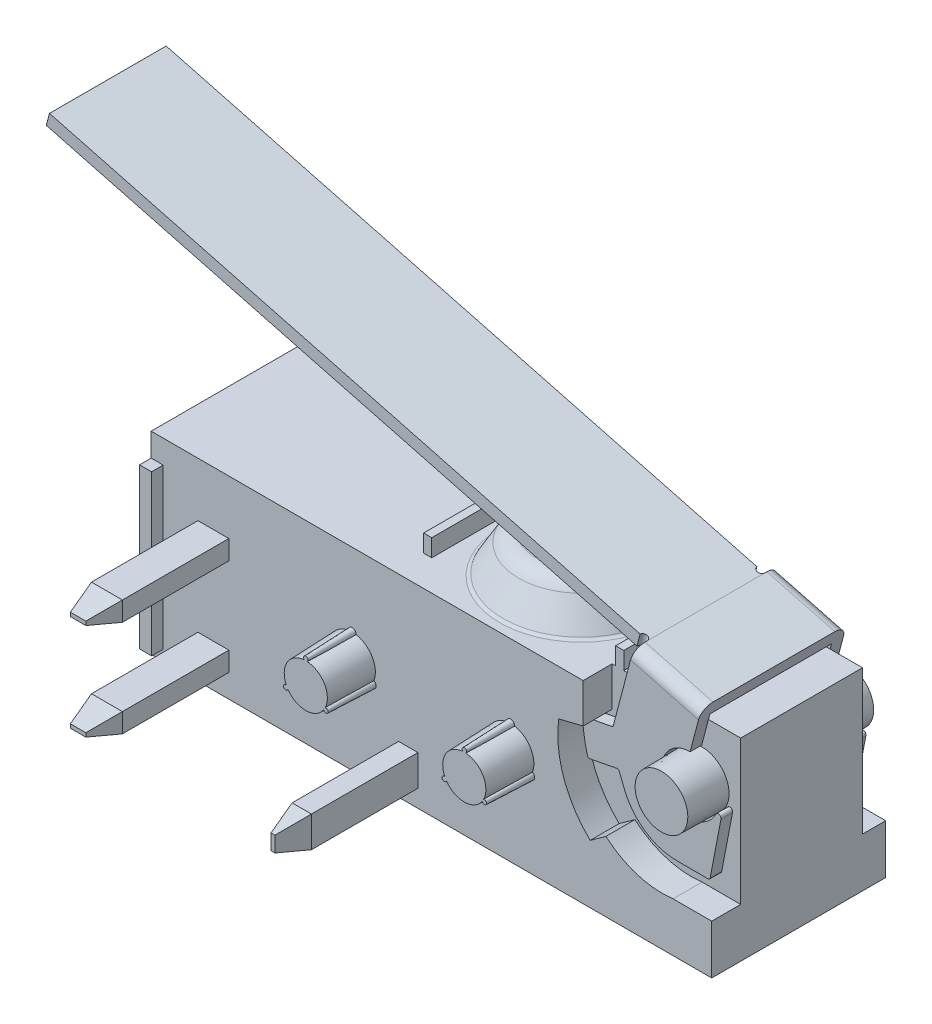
SolidWorks part; units mm, degrees
ref_plane "Front Plane" through (0, 0, 0) normal (0, 0, 1) x (1, 0, 0)
ref_plane "Top Plane" through (0, 0, 0) normal (0, 1, 0) x (1, 0, 0)
ref_plane "Right Plane" through (0, 0, 0) normal (1, 0, 0) x (0, 0, -1)
sketch "Sketch1" plane through (0, 0, 0) normal (0, 0, 1) x (1, 0, 0)
  line L0 (0, 0) -> (0, -2.5) construction
  line L1 (0, -2.5) -> (5.2, -2.5)
  line L2 (5.2, -2.5) -> (5.2, 2.5)
  line L3 (5.2, 2.5) -> (-9.3, 2.5)
  line L4 (-9.3, 2.5) -> (-9.3, -2.5)
  line L5 (0, -2.5) -> (-9.3, -2.5)
  dimension "D1" = 2.5
  dimension "D2" = 5.2
  dimension "D3" = 5
  dimension "D4" = 14.5
extrude "Boss-Extrude1" add sketch "Sketch1" against normal blind 4.5
sketch "Sketch2" plane through (0, 0, 0) normal (0, 0, 1) x (1, 0, 0)
  line L0 (0, 0) -> (0, 0.6) construction
  line L1 (0, 0) -> (0.5196, -0.3) construction
  line L2 (0, 0) -> (0, -2.5) construction
  line L3 (-9.3, -2.5) -> (5.2, -2.5) construction
  line L4 (-4.1, 0) -> (-4.1, -2.5)
  line L5 (-4.1, 0) -> (-3.5804, -0.3) construction
  line L6 (-4.1, 0) -> (-4.1, 0.6) construction
  arc A0 (-0.0997, 0.5917) -> (-0.5622, -0.2095) centre (0, 0) ccw
  arc A1 (-4.6622, -0.2095) -> (-4.5626, -0.3821) centre (-4.6196, -0.3) ccw
  arc A2 (0.0997, 0.5917) -> (-0.0997, 0.5917) centre (0, 0.6) ccw
  arc A3 (0.4626, -0.3821) -> (0.5622, -0.2095) centre (0.5196, -0.3) ccw
  arc A4 (-0.5622, -0.2095) -> (-0.4626, -0.3821) centre (-0.5196, -0.3) ccw
  arc A5 (-0.4626, -0.3821) -> (0.4626, -0.3821) centre (0, 0) ccw
  arc A6 (0.5622, -0.2095) -> (0.0997, 0.5917) centre (0, 0) ccw
  arc A7 (-3.5378, -0.2095) -> (-4.0003, 0.5917) centre (-4.1, 0) ccw
  arc A8 (-4.0003, 0.5917) -> (-4.1997, 0.5917) centre (-4.1, 0.6) ccw
  arc A9 (-4.1997, 0.5917) -> (-4.6622, -0.2095) centre (-4.1, 0) ccw
  arc A10 (-3.6374, -0.3821) -> (-3.5378, -0.2095) centre (-3.5804, -0.3) ccw
  arc A11 (-4.5626, -0.3821) -> (-3.6374, -0.3821) centre (-4.1, 0) ccw
  dimension "D1" = 3
  dimension "D2" = 120
  dimension "D3" = 0.6
  dimension "D4" = 4.1
extrude "Boss-Extrude3" add sketch "Sketch2" along normal blind 1.2 draft 2 contours A1 A11 A10 A7 A8 A9 | A3 A6 A2 A0 A4 A5 region at (0, 0, 0) region at (-4.6041, 0.291, 0)
sketch "Sketch3" plane through (0, 0, 0) normal (0, 0, 1) x (1, 0, 0)
  line L0 (0, 0) -> (0, -2.5) construction
  line L1 (-9.3, -2.5) -> (5.2, -2.5) construction
  line L3 (-9.3, -2.5) -> (5.2, -2.5)
  line L5 (-2.9, -2.05) -> (-2.9, -1.25)
  line L6 (-7.29, -1.9) -> (-7.29, -1.4)
  line L7 (-8.09, -1.9) -> (-8.09, -1.4)
  line L8 (-2.9, -1.25) -> (-2.4, -1.25)
  line L9 (-2.4, -2.05) -> (-2.4, -1.25)
  line L10 (-2.9, -2.05) -> (-2.4, -2.05)
  line L11 (-7.29, -1.4) -> (-8.09, -1.4)
  line L12 (-7.29, -1.9) -> (-8.09, -1.9)
  line L13 (-7.69, -1.9) -> (-7.69, -1.65) construction
  line L14 (-7.69, 0.6) -> (-7.69, 0.85) construction
  line L15 (-7.29, 1.1) -> (-8.09, 1.1)
  line L16 (-8.09, 0.6) -> (-8.09, 1.1)
  line L17 (-7.29, 0.6) -> (-7.29, 1.1)
  line L18 (-7.29, 0.6) -> (-8.09, 0.6)
  point P5 (-2.65, 0)
  point P6 (-2.65, -2.5)
  point P7 (-9.3, -1.65)
  point P8 (5.2, -1.65)
  point P17 (-2.9, -1.65)
  point P23 (-7.69, -1.9)
  point P29 (-7.69, 0.6)
extrude "Boss-Extrude4" add sketch "Sketch3" along normal blind 3.5 separate body contours L5 L10 L9 L8 | L12 L6 L11 L7 | L18 L17 L15 L16 region at (-2.65, -1.65, 0) region at (-7.69, -1.65, 0) region at (-7.69, 0.85, 0)
chamfer "Chamfer1" distance 0.2 angle 75 4 edges at (-2.65, -1.25, 3.5) (-2.4, -1.65, 3.5) (-2.65, -2.05, 3.5) (-2.9, -1.65, 3.5) first distance on face at (-2.65, -1.65, 3.5)
chamfer "Chamfer2" distance 0.2 angle 75 4 edges at (-7.69, 0.6, 3.5) (-7.29, 0.85, 3.5) (-7.69, 1.1, 3.5) (-8.09, 0.85, 3.5) first distance on face at (-7.69, 0.85, 3.5)
chamfer "Chamfer3" distance 0.2 angle 75 4 edges at (-7.69, -1.4, 3.5) (-7.29, -1.65, 3.5) (-7.69, -1.9, 3.5) (-8.09, -1.65, 3.5) first distance on face at (-7.69, -1.65, 3.5)
sketch "Sketch5" plane through (0, 0, 0) normal (0, 0, 1) x (1, 0, 0)
  line L0 (1.8737, 2.5) -> (5.2, 2.5)
  line L3 (5.2, -1.2263) -> (4.2, -1.2263)
  line L5 (1.8737, 1.4816) -> (1.8737, 2.5)
  line L6 (1.8737, 1.4816) -> (1.242, 1.3256)
  line L7 (5.2, 2.5) -> (5.2, -1.2263)
  line L8 (2.0554, -0.9882) -> (2.4632, -0.6956)
  arc A0 (1.242, 1.3256) -> (2.0554, -0.9882) centre (3.9209, 0.9675) ccw
  arc A1 (2.4632, -0.6956) -> (4.2, -1.2263) centre (3.9209, 0.9675) ccw
  line M9 (5.2, -2.5) -> (5.2, 2.5)
  line M10 (5.2, 2.5) -> (-9.3, 2.5)
extrude "Cut-Extrude1" cut sketch "Sketch5" against normal blind 0.75 from surface contours L8 A1 L3 L5 L6 A0 M9 M10 region at (3.4128, 0.6847, 0) starting at face at (-4.1, 0, 0)
sketch "Sketch6" plane through (0, 0, -0.75) normal (0, 0, 1) x (1, 0, 0)
  line L0 (0, 0) -> (0, 2.5) construction
  line L1 (1.8737, 2.5) -> (-9.3, 2.5) construction
  circle A0 centre (4.2, 1.1) radius 0.7
extrude "Boss-Extrude6" add sketch "Sketch6" along normal blind 1.05 draft 1
sketch "Sketch7" plane through (0, 0, -4.5) normal (0, 0, -1) x (-1, 0, 0)
  line L1 (-1.8737, 1.4816) -> (-1.8737, 2.5) construction
  line L2 (-1.8737, 2.5) -> (-5.2, 2.5) construction
  line L3 (-5.2, 2.5) -> (-5.2, -1.2263) construction
  line L4 (-5.2, -1.2263) -> (-4.2, -1.2263) construction
  line L5 (-2.0554, -0.9882) -> (-2.4632, -0.6956) construction
  line L6 (-1.8737, 1.4531) -> (-1.2749, 1.2919)
  line L7 (-1.8737, 1.4531) -> (-1.8737, 2.5)
  line L8 (-1.8737, 2.5) -> (-5.2, 2.5)
  line L9 (-5.2, 2.5) -> (-5.2, -1.2263)
  line L10 (-5.2, -1.2263) -> (-4.2, -1.2263)
  line L11 (-2.086, -0.9663) -> (-2.4632, -0.6956)
  arc A0 (-4.2, -1.2263) -> (-2.4632, -0.6956) centre (-3.9209, 0.9675) ccw construction
  arc A2 (-4.2, -1.2263) -> (-2.4632, -0.6956) centre (-3.9209, 0.9675) ccw
  arc A3 (-2.086, -0.9663) -> (-1.2749, 1.2919) centre (-3.9209, 0.9675) ccw
  line M3 (9.3, 2.5) -> (-5.2, 2.5)
  line M4 (-5.2, 2.5) -> (-5.2, -2.5)
extrude "Cut-Extrude2" cut sketch "Sketch7" against normal blind 0.6 contours L11 A3 L6 L7 L10 A2 M3 M4 region at (3.4299, 0.6877, -4.5)
sketch "Sketch8" plane through (0, 0, -3.9) normal (0, 0, -1) x (-1, 0, 0)
  circle A1 centre (-4.2, 1.1) radius 0.7
  circle A2 centre (-4.2, 1.1) radius 0.7
  dimension "D1" = 0
extrude "Boss-Extrude7" add sketch "Sketch8" along normal blind 0.6 draft 1
sketch "Sketch9" plane through (0, 2.5, 0) normal (0, 1, 0) x (1, 0, 0)
  line L0 (4.2, -0.3) -> (4.2, 4.5) construction
  line L1 (3.5183, -0.3) -> (4.8817, -0.3) construction
  line L3 (5.2, 2.325) -> (-0.5, 2.325) construction
  line L4 (5.2, 3.9) -> (5.2, 0.75) construction
  circle A0 centre (-0.5, 2.325) radius 2.05
extrude "Boss-Extrude8" add sketch "Sketch9" along normal blind 1 draft 30
fillet "Fillet1" radius 0.5 1 edges at (-1.9726, 3.5, -2.325)
fillet "Fillet2" radius 0.1 1 edges at (-2.55, 2.5, -2.325)
sketch "Sketch10" plane through (0, 3.5, 0) normal (0, 1, 0) x (1, 0, 0)
  circle A0 centre (-0.5, 2.325) radius 0.8
extrude "Cut-Extrude3" cut sketch "Sketch10" against normal blind 0.2
sketch "Sketch11" plane through (0, 3.3, 0) normal (0, 1, 0) x (1, 0, 0)
  circle A0 centre (-0.5, 2.325) radius 0.7
extrude "Boss-Extrude9" add sketch "Sketch11" along normal blind 0.4
dome "Dome1" faces to dome 1 distance 0.2 reverse direction no elliptical dome no face at (-1.2, 3.7, -2.325) parameters "D1"=0.2
sketch "Sketch12" plane through (0, 2.5, 0) normal (0, 1, 0) x (1, 0, 0)
  line L0 (2.086, 3.9) -> (1.2551, 3.9) construction
  line L1 (1.9653, 3.9) -> (2.1753, 3.9)
  line L2 (1.9653, 3.9) -> (1.9653, 0.75)
  line L3 (1.9653, 0.75) -> (2.1753, 0.75)
  line L4 (2.1753, 3.9) -> (2.1753, 0.75)
  line L5 (1.8737, 0.75) -> (5.2, 0.75) construction
  line L6 (-3.0447, 3.942) -> (-3.0447, 0.792)
  line L7 (-2.8347, 3.942) -> (-2.8347, 0.792)
  line L8 (-3.0447, 3.942) -> (-2.8347, 3.942)
  line L9 (-3.0447, 0.792) -> (-2.8347, 0.792)
  dimension "D1" = 4.8
  dimension "D2" = 0.21
  dimension "D3" = 0.21
extrude "Boss-Extrude10" add sketch "Sketch12" along normal blind 0.45
sketch "Sketch14" plane through (0, 0, 0) normal (0, 0, 1) x (1, 0, 0)
  line L0 (-9.3, 2.5) -> (-9.3, -2.5) construction
  line L1 (-9.3, -2.229) -> (-8.9887, -2.229)
  line L2 (-9.3, -2.229) -> (-9.3, 1.8958)
  line L3 (-9.3, 1.8958) -> (-8.9887, 1.8958)
  line L4 (-8.9887, -2.229) -> (-8.9887, 1.8958)
extrude "Boss-Extrude11" add sketch "Sketch14" along normal blind 0.3
sketch "Sketch16" plane through (0, 0, -3.9) normal (0, 0, -1) x (-1, 0, 0)
  line L0 (-2.7266, 3.4139) -> (-2.6958, 3.2969)
  line L1 (-4.6587, -0.7751) -> (-3.8482, -0.7751)
  line L2 (-4.1913, 0.0356) -> (-4.1913, 2.1598) construction
  line L3 (-2.165, 1.3934) -> (-1.448, 1.2557)
  line L4 (-2.4958, 0.1409) -> (-2.3555, 0.4894)
  line L5 (-4.4842, 2.9511) -> (-2.7266, 3.4139)
  line L6 (-2.6958, 3.2969) -> (-2.4885, 2.5094)
  line L7 (-4.3679, 2.5094) -> (-4.1913, 1.8389)
  line L8 (-5.2534, 1.0977) -> (-3.1293, 1.0977) construction
  line L9 (-2.2992, 0.5201) -> (-1.5942, 0.3847)
  line L10 (-4.4842, 2.9511) -> (-4.3679, 2.5094)
  line L11 (-4.9901, 0.7303) -> (-4.7083, -0.7342)
  line L12 (-2.4885, 2.5094) -> (-2.2043, 1.4301)
  arc A0 (-4.8659, 0.7906) -> (-4.1913, 1.8389) centre (-4.1913, 1.0977) ccw
  arc A1 (-4.8659, 0.7906) -> (-4.9901, 0.7303) centre (-4.9199, 0.7438) ccw
  arc A2 (-3.8482, -0.7751) -> (-2.4958, 0.1409) centre (-3.8482, 0.6814) ccw
  arc A3 (-2.2043, 1.4301) -> (-2.165, 1.3934) centre (-2.1555, 1.4429) ccw
  arc A4 (-1.5942, 0.3847) -> (-1.5359, 0.4214) centre (-1.5847, 0.4343) ccw
  arc A5 (-1.5359, 0.4214) -> (-1.4072, 1.2027) centre (-5.6016, 1.4926) ccw
  arc A6 (-4.7083, -0.7342) -> (-4.6587, -0.7751) centre (-4.6587, -0.7246) ccw
  arc A7 (-1.4072, 1.2027) -> (-1.448, 1.2557) centre (-1.4575, 1.2062) ccw
  arc A8 (-2.2992, 0.5201) -> (-2.3555, 0.4894) centre (-2.3087, 0.4706) ccw
extrude "Boss-Extrude12" add sketch "Sketch16" along normal blind 0.3 separate body
ref_plane "Plane1" through (0, 0, -2.33) normal (0, 0, 1) x (1, 0, 0)
pattern_linear "LPattern1" count 2 spacing 3.45 along (0, 0, 1) of "Boss-Extrude12"
sketch "Sketch17" plane through (0, 0, -3.9) normal (0, 0, 1) x (1, 0, 0)
  line L0 (2.7266, 3.4139) -> (4.4842, 2.9511) construction
  line L1 (2.6958, 3.2969) -> (2.7266, 3.4139) construction
  line L2 (2.7266, 3.4139) -> (4.4842, 2.9511)
  line L3 (2.6452, 3.1045) -> (2.7266, 3.4139)
  line L4 (2.6452, 3.1045) -> (4.4027, 2.6417)
  line L5 (4.4027, 2.6417) -> (4.4842, 2.9511)
  dimension "D1" = 0.32
extrude "Boss-Extrude13" add sketch "Sketch17" along normal up to surface (3.15 mm away) up to face at (3.3735, 2.8115, -0.75)
sketch "Sketch18" plane through (1.7092, -0.4501, 0) normal (-0.967, 0.2546, 0) x (0, 0, 1)
  line L1 (-4.2, 3.9957) -> (-0.45, 3.9957)
  line L2 (-4.2, 3.9957) -> (-4.2, 3.6757)
  line L3 (-4.2, 3.6757) -> (-0.45, 3.6757)
  line L4 (-0.45, 3.9957) -> (-0.45, 3.6757)
  line L6 (-4.2, 3.9957) -> (-0.45, 3.9957) construction
  dimension "D1" = 0.32
extrude "Boss-Extrude14" add sketch "Sketch18" along normal blind 16
sketch "Sketch22" plane through (1.0174, 3.864, 0) normal (0.2546, 0.967, 0) x (0.967, -0.2546, 0)
  line L0 (1.7675, 0.45) -> (1.7675, 0.8156)
  line L1 (1.7675, 4.2) -> (1.7675, 0.45) construction
  line L2 (1.5669, 0.8156) -> (-14.2325, 0.8156)
  line L4 (-14.2325, 0.45) -> (1.7675, 0.45) construction
  line L5 (-14.2325, 0.45) -> (1.7675, 0.45)
  line L6 (1.7675, 2.325) -> (-14.2325, 2.325) construction
  line L7 (-14.2325, 0.45) -> (-14.2325, 4.2) construction
  line L8 (1.7675, 4.2) -> (1.7675, 3.8344)
  line L9 (-14.2325, 4.2) -> (1.7675, 4.2)
  line L10 (-14.2325, 4.2) -> (1.7675, 4.2) construction
  line L11 (1.5675, 3.8344) -> (-14.2325, 3.8344)
  line L12 (-14.2325, 4.2) -> (-14.2325, 3.8344)
  line L13 (-14.2325, 0.45) -> (-14.2325, 0.8156)
  arc A0 (1.5669, 0.8156) -> (1.7675, 0.8156) centre (1.6672, 0.7998) cw
  arc A1 (1.5669, 3.8344) -> (1.7675, 3.8344) centre (1.6672, 3.8502) ccw
  point P19 (-14.2325, 0.8156)
  point P22 (1.7675, 0.8156)
  point P25 (-14.2325, 3.8344)
  point P28 (1.7675, 3.8344)
  line M1 (1.7675, 0.45) -> (1.7675, 4.2)
  line M2 (1.7675, 4.2) -> (-14.2325, 4.2)
  line M3 (-14.2325, 4.2) -> (-14.2325, 0.45)
  line M4 (-14.2325, 0.45) -> (1.7675, 0.45)
extrude "Cut-Extrude4" cut sketch "Sketch22" along direction (0.2546, 0.967, 0) on the side against the normal up to next (0.32 mm away) contours A1 L11 M1 M2 M3 | A0 L2 M3 M4 M1 region at (-4.9927, 5.4465, -0.6333) region at (-4.9927, 5.4465, -4.0167)
fillet "Fillet3" radius 0.3 2 edges at (3.6054, 3.1825, -4.2) (3.6054, 3.1825, -0.45)
